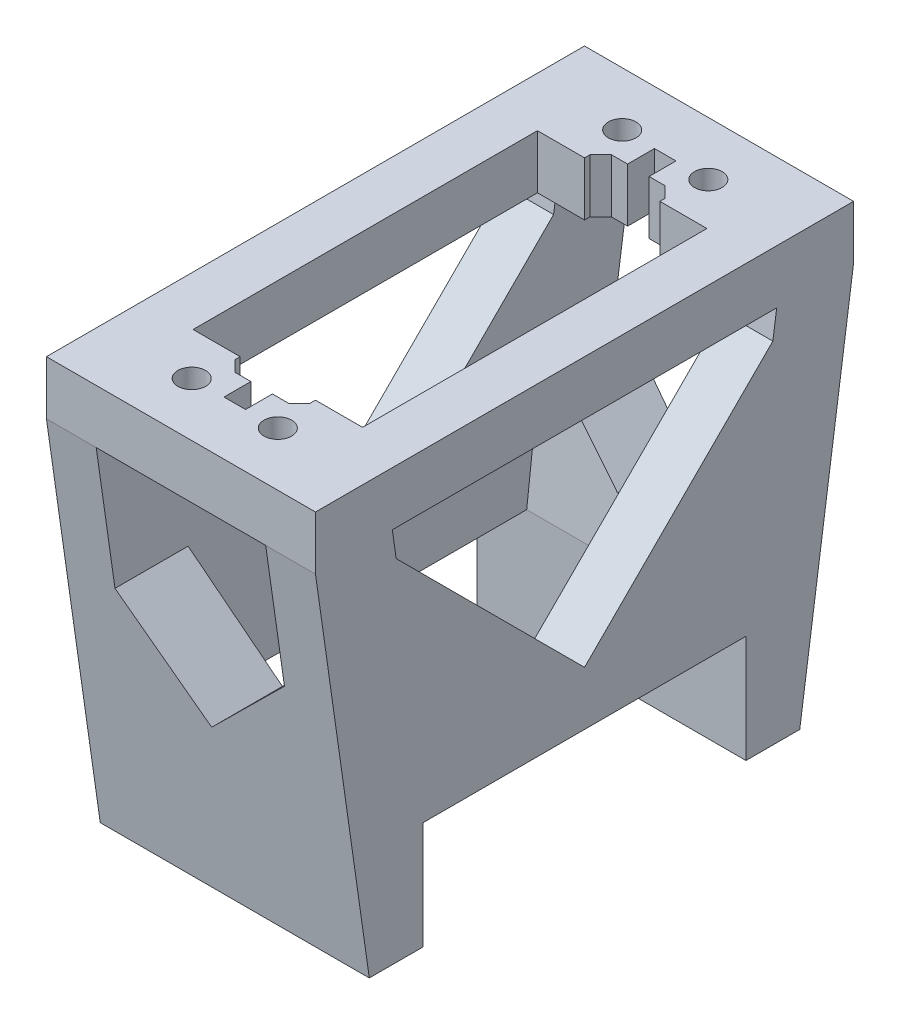
SolidWorks part; units mm, degrees
material "ABS"
ref_plane "Front Plane" through (0, 0, 0) normal (0, 0, 1) x (1, 0, 0)
ref_plane "Top Plane" through (0, 0, 0) normal (0, 1, 0) x (1, 0, 0)
ref_plane "Right Plane" through (0, 0, 0) normal (1, 0, 0) x (0, 0, -1)
sketch "Sketch2" plane through (0, 0, 0) normal (0, 0, 1) x (1, 0, 0)
  line L1 (-15.875, 3.175) -> (15.875, 3.175)
  line L2 (-15.875, 3.175) -> (-15.875, -3.175)
  line L3 (-15.875, -3.175) -> (15.875, -3.175)
  line L4 (15.875, 3.175) -> (15.875, -3.175)
  line L5 (15.875, 3.175) -> (-15.875, -3.175) construction
  line L6 (15.875, -3.175) -> (-15.875, 3.175) construction
  dimension "D1" = 6.35
  dimension "D2" = 31.75
extrude "Boss-Extrude2" add sketch "Sketch2" along normal mid plane 63.5
sketch "Sketch3" plane through (0, 3.175, 0) normal (0, 1, 0) x (1, 0, 0)
  line L0 (0, 20.32) -> (0, 31.75) construction
  line L1 (10, 20.32) -> (-10, 20.32)
  line L2 (10, 20.32) -> (10, -20.32)
  line L3 (10, -20.32) -> (-10, -20.32)
  line L4 (-10, 20.32) -> (-10, -20.32)
  line L5 (0, 0) -> (0, 20.32) construction
  line L6 (0, -31.75) -> (0, -20.32) construction
  line L7 (15.875, -31.75) -> (-15.875, -31.75) construction
  line L8 (15.875, 31.75) -> (-15.875, 31.75) construction
  dimension "D1" = 40.64
  dimension "D2" = 20
extrude "Cut-Extrude1" cut sketch "Sketch3" against normal through all
sketch "Sketch4" plane through (0, 3.175, 0) normal (0, 1, 0) x (1, 0, 0)
  line L0 (0, 20.32) -> (0, -20.32) construction
  line L3 (10, 20.32) -> (-10, 20.32) construction
  line L5 (-10, 0) -> (0, 0) construction
  line L6 (-10, 20.32) -> (-10, -20.32) construction
  circle A0 centre (-5.08, 25.4) radius 1.632
  circle A1 centre (5.08, 25.4) radius 1.632
  circle A2 centre (-5.08, -25.4) radius 1.6319
  circle A3 centre (5.08, -25.4) radius 1.6319
  dimension "D1" = 3.2639
  dimension "D2" = 50.8
  dimension "D3" = 10.16
extrude "Cut-Extrude2" cut sketch "Sketch4" against normal through all
sketch "Sketch7" plane through (0, 3.175, 0) normal (0, 1, 0) x (1, 0, 0)
  line L0 (-10, 0) -> (10, 0) construction
  line L2 (-1.27, -15.24) -> (1.27, -15.24)
  line L3 (-1.27, -15.24) -> (-1.27, -25.4)
  line L4 (-1.27, -25.4) -> (1.27, -25.4)
  line L5 (1.27, -15.24) -> (1.27, -25.4)
  line L6 (-1.27, -15.24) -> (1.27, -25.4) construction
  line L7 (-1.27, -25.4) -> (1.27, -15.24) construction
  line L9 (-1.27, 15.24) -> (1.27, 15.24)
  line L10 (-1.27, 15.24) -> (-1.27, 25.4)
  line L11 (-1.27, 25.4) -> (1.27, 25.4)
  line L12 (1.27, 15.24) -> (1.27, 25.4)
  line L13 (-1.27, 15.24) -> (1.27, 25.4) construction
  line L14 (-1.27, 25.4) -> (1.27, 15.24) construction
  line L15 (4.445, -22.225) -> (-4.445, -22.225)
  line L16 (4.445, -22.225) -> (4.445, 22.225)
  line L17 (4.445, 22.225) -> (-4.445, 22.225)
  line L18 (-4.445, -22.225) -> (-4.445, 22.225)
  line L19 (4.445, -22.225) -> (-4.445, 22.225) construction
  line L20 (4.445, 22.225) -> (-4.445, -22.225) construction
  line L23 (10, 20.32) -> (-10, 20.32) construction
  line L24 (-10, -20.32) -> (10, -20.32) construction
  point P0 (0, -20.32)
  point P7 (0, 20.32)
  point P14 (0, 0)
  dimension "D1" = 10.16
  dimension "D2" = 2.54
  dimension "D3" = 8.89
  dimension "D4" = 44.45
extrude "Cut-Extrude4" cut sketch "Sketch7" against normal through all contours L18 L10 L17 | L16 L17 L12 | L15 L16 L5 | L18 L15 L3 | L12 L17 L10 | L17 L12 L11 L10 | L15 L5 L3 | L5 L15 L3 L4 region at (0, 3.175, 0) region at (0, 3.175, 18.7325) region at (0, 3.175, 23.8125) region at (0, 3.175, -18.7325) region at (0, 3.175, -23.8125)
chamfer "Chamfer1" distance 1.27 angle 45 4 edges at (-4.445, 0, 22.225) (4.445, 0, 22.225) (4.445, 0, -22.225) (-4.445, 0, -22.225)
sketch "Sketch6" plane through (0, -3.175, 0) normal (0, -1, 0) x (1, 0, 0)
  line L1 (-1.905, 27.2331) -> (-5.08, 29.0662)
  line L2 (-5.08, 29.0662) -> (-8.255, 27.2331)
  line L3 (-8.255, 27.2331) -> (-8.255, 23.5669)
  line L4 (-8.255, 23.5669) -> (-5.08, 21.7338)
  line L5 (-5.08, 21.7338) -> (-1.905, 23.5669)
  line L6 (-1.905, 23.5669) -> (-1.905, 27.2331)
  line L7 (8.255, 27.2331) -> (5.08, 29.0662)
  line L8 (5.08, 29.0662) -> (1.905, 27.2331)
  line L9 (1.905, 27.2331) -> (1.905, 23.5669)
  line L10 (1.905, 23.5669) -> (5.08, 21.7338)
  line L11 (5.08, 21.7338) -> (8.255, 23.5669)
  line L12 (8.255, 23.5669) -> (8.255, 27.2331)
  line L13 (8.255, -23.5669) -> (5.08, -21.7338)
  line L14 (5.08, -21.7338) -> (1.905, -23.5669)
  line L15 (1.905, -23.5669) -> (1.905, -27.2331)
  line L16 (1.905, -27.2331) -> (5.08, -29.0662)
  line L17 (5.08, -29.0662) -> (8.255, -27.2331)
  line L18 (8.255, -27.2331) -> (8.255, -23.5669)
  line L19 (-1.905, -23.5669) -> (-5.08, -21.7338)
  line L20 (-5.08, -21.7338) -> (-8.255, -23.5669)
  line L21 (-8.255, -23.5669) -> (-8.255, -27.2331)
  line L22 (-8.255, -27.2331) -> (-5.08, -29.0662)
  line L23 (-5.08, -29.0662) -> (-1.905, -27.2331)
  line L24 (-1.905, -27.2331) -> (-1.905, -23.5669)
  circle A0 centre (-5.08, 25.4) radius 3.175 construction
  circle A1 centre (5.08, 25.4) radius 3.175 construction
  circle A2 centre (5.08, -25.4) radius 3.175 construction
  circle A3 centre (-5.08, -25.4) radius 3.175 construction
  dimension "D1" = 6.35
extrude "Cut-Extrude3" cut sketch "Sketch6" against normal blind 2.3813
sketch "Sketch10" plane through (15.875, 0, 0) normal (1, 0, 0) x (0, 0, -1)
  line L0 (25.4, -47.625) -> (19.05, -47.625)
  line L2 (19.05, -47.625) -> (19.05, -34.925)
  line L3 (19.05, -34.925) -> (-19.05, -34.925)
  line L4 (-19.05, -34.925) -> (-19.05, -47.625)
  line L5 (-19.05, -47.625) -> (-25.4, -47.625)
  line L6 (-19.05, -28.575) -> (-22.6786, -3.175)
  line L7 (-19.05, -28.575) -> (19.05, -28.575)
  line L8 (22.6786, -3.175) -> (31.75, -3.175)
  line L9 (19.05, -28.575) -> (22.6786, -3.175)
  line L10 (0, 0) -> (0, -28.575) construction
  line L13 (-31.75, -3.175) -> (31.75, -3.175) construction
  line L14 (-25.4, -47.625) -> (-31.75, -3.175)
  line L15 (-31.75, -3.175) -> (-22.6786, -3.175)
  line L16 (31.75, -3.175) -> (25.4, -47.625)
  dimension "D1" = 38.1
  dimension "D2" = 6.35
  dimension "D3" = 6.35
  dimension "D4" = 6.35
  dimension "D6" = 12.7
  dimension "D7" = 25.4
extrude "Boss-Extrude5" add sketch "Sketch10" against normal through all
sketch "Sketch12" plane through (0, 0, 31.75) normal (0, 0, 1) x (1, 0, 0)
  line L0 (-15.875, -3.175) -> (15.875, -3.175) construction
  line L1 (-10, -3.175) -> (10, -3.175)
  line L2 (-10, -3.175) -> (-10, -28.575)
  line L3 (-10, -28.575) -> (10, -28.575)
  line L4 (10, -3.175) -> (10, -28.575)
  line L5 (-15.875, -28.575) -> (15.875, -28.575) construction
  line L8 (10, -3.175) -> (10, 3.175) construction
  line L9 (-10, -3.175) -> (-10, 3.175) construction
extrude "Cut-Extrude5" cut sketch "Sketch12" against normal through all
sketch "Sketch13" plane through (0, -4.5085, -31.5595) normal (0, -0.1414, -0.9899) x (-1, 0, 0)
  line L0 (0, -24.3108) -> (-10, -14.3108)
  line L1 (-10, -24.3108) -> (10, -24.3108) construction
  line L2 (-10, 1.347) -> (-10, -24.3108) construction
  line L3 (0, -24.3108) -> (10, -14.3108)
  line L4 (10, -24.3108) -> (10, 1.347) construction
  line L5 (10, -14.3108) -> (10, -24.3108)
  line L6 (10, -24.3108) -> (-10, -24.3108)
  line L7 (-10, -24.3108) -> (-10, -14.3108)
  line M1 (10, 1.347) -> (10, -24.3108)
  line M2 (10, -24.3108) -> (-10, -24.3108)
  line M3 (-10, -24.3108) -> (-10, 1.347)
  dimension "D1" = 45
extrude "Boss-Extrude6" add sketch "Sketch13" along direction (0, 0, 1) on the side against the normal up to vertex (8.9803 mm away) contours L3 M2 M1 | L0 M2 M3 region at (6.6667, -25.2752, -28.5928) region at (-6.6667, -25.2752, -28.5928) up to point (-10, -3.175, -22.6786)
sketch "Sketch14" plane through (0, -4.5085, 31.5595) normal (0, -0.1414, 0.9899) x (1, 0, 0)
  line L0 (0, -24.3108) -> (10, -14.3108)
  line L1 (-10, -24.3108) -> (10, -24.3108) construction
  line L2 (10, -24.3108) -> (10, 1.347) construction
  line L3 (10, -14.3108) -> (10, -24.3108)
  line L4 (10, -24.3108) -> (0, -24.3108)
  line L5 (0, -24.3108) -> (-10, -24.3108)
  line L6 (-10, -24.3108) -> (-10, -14.3108)
  line L7 (-10, 1.347) -> (-10, -24.3108) construction
  line L8 (-10, -14.3108) -> (0, -24.3108)
  line L9 (0, -24.3108) -> (-0.4291, -24.5165)
  line M1 (-10, -24.3108) -> (-10, 1.347)
  line M7 (10, 1.347) -> (10, -24.3108)
  line M8 (10, -24.3108) -> (-10, -24.3108)
  dimension "D1" = 45
extrude "Boss-Extrude7" add sketch "Sketch14" along direction (0, 0, 1) on the side against the normal up to surface (8.9803 mm away) contours L8 M1 M8 | L0 M8 M7 region at (6.6667, -25.2752, 28.5928) region at (-6.6667, -25.2752, 28.5928) up to face at (12.9375, -15.875, 20.8643)
sketch "Sketch15" plane through (15.875, 0, 0) normal (1, 0, 0) x (0, 0, -1)
  line L0 (0, -28.575) -> (-22.225, -6.35)
  line L1 (19.05, -28.575) -> (-19.05, -28.575) construction
  line L2 (-19.05, -28.575) -> (-22.6786, -3.175) construction
  line L3 (-22.225, -6.35) -> (-19.05, -28.575)
  line L4 (-19.05, -28.575) -> (0, -28.575)
  line L5 (0, -28.575) -> (22.225, -6.35)
  line L6 (22.6786, -3.175) -> (19.05, -28.575) construction
  line L7 (22.225, -6.35) -> (19.05, -28.575)
  line L8 (19.05, -28.575) -> (0, -28.575)
  line M1 (-19.05, -28.575) -> (-22.6786, -3.175)
  line M3 (22.6786, -3.175) -> (19.05, -28.575)
  line M4 (19.05, -28.575) -> (-19.05, -28.575)
  dimension "D1" = 45
extrude "Boss-Extrude8" add sketch "Sketch15" along direction (1, 0, 0) on the side against the normal up to surface (31.75 mm away) contours L5 M4 M3 | L0 M4 M1 region at (15.875, -21.1667, 13.7583) region at (15.875, -21.1667, -13.7583) up to face at (-15.875, -15.875, 0)
sketch "Sketch16" plane through (0, -3.175, 0) normal (0, -1, 0) x (1, 0, 0)
  line L1 (-10, 22.6786) -> (10, 22.6786)
  line L2 (-10, 22.6786) -> (-10, -22.6786)
  line L3 (-10, -22.6786) -> (10, -22.6786)
  line L4 (10, 22.6786) -> (10, -22.6786)
sketch "Sketch18" plane through (0, -34.925, 0) normal (0, -1, 0) x (1, 0, 0)
  line L0 (-10, 22.6786) -> (-10, -22.6786) construction
  line L1 (-10, 19.05) -> (10, 19.05)
  line L2 (-10, 19.05) -> (-10, -19.05)
  line L3 (-10, -19.05) -> (10, -19.05)
  line L4 (10, 19.05) -> (10, -19.05)
  line L5 (-15.875, 19.05) -> (15.875, 19.05) construction
  line L6 (10, 22.6786) -> (10, -22.6786) construction
  line L7 (-15.875, -19.05) -> (15.875, -19.05) construction
loft "Cut-Loft1" cut profiles "Sketch16", "Sketch18" connector at (10, -3.175, 22.6786) connector at (10, -34.925, 19.05)
